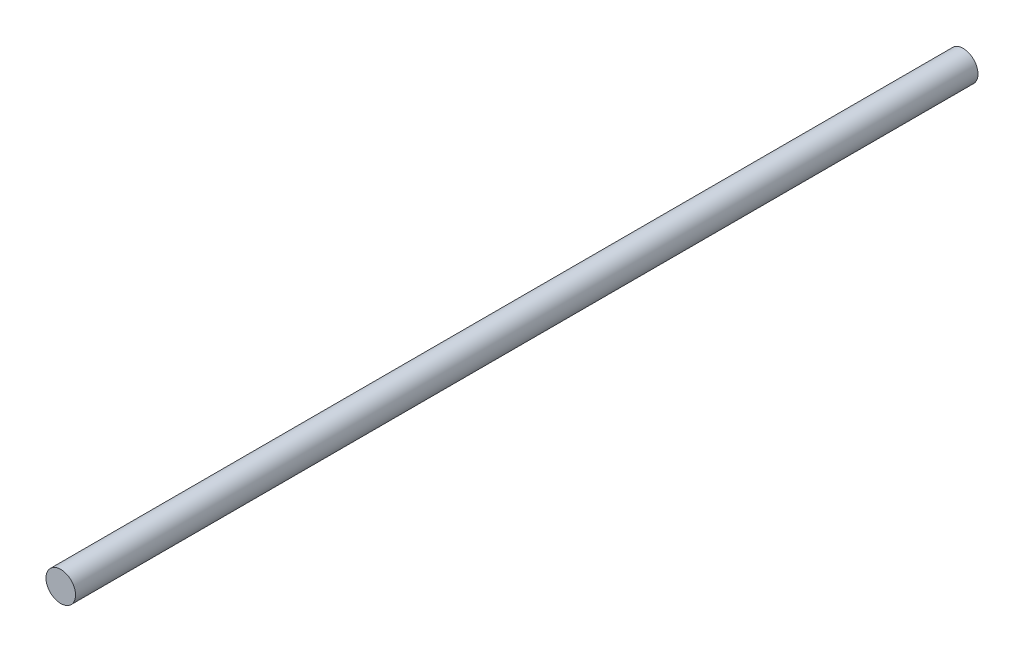
SolidWorks part; units mm, degrees
ref_plane "Front Plane" through (0, 0, 0) normal (0, 0, 1) x (1, 0, 0)
ref_plane "Top Plane" through (0, 0, 0) normal (0, 1, 0) x (1, 0, 0)
ref_plane "Right Plane" through (0, 0, 0) normal (1, 0, 0) x (0, 0, -1)
sketch "Sketch1" plane through (0, 0, 0) normal (0, 0, 1) x (1, 0, 0)
  circle A0 centre (0, 0) radius 10
extrude "Boss-Extrude1" add sketch "Sketch1" along normal blind 610
